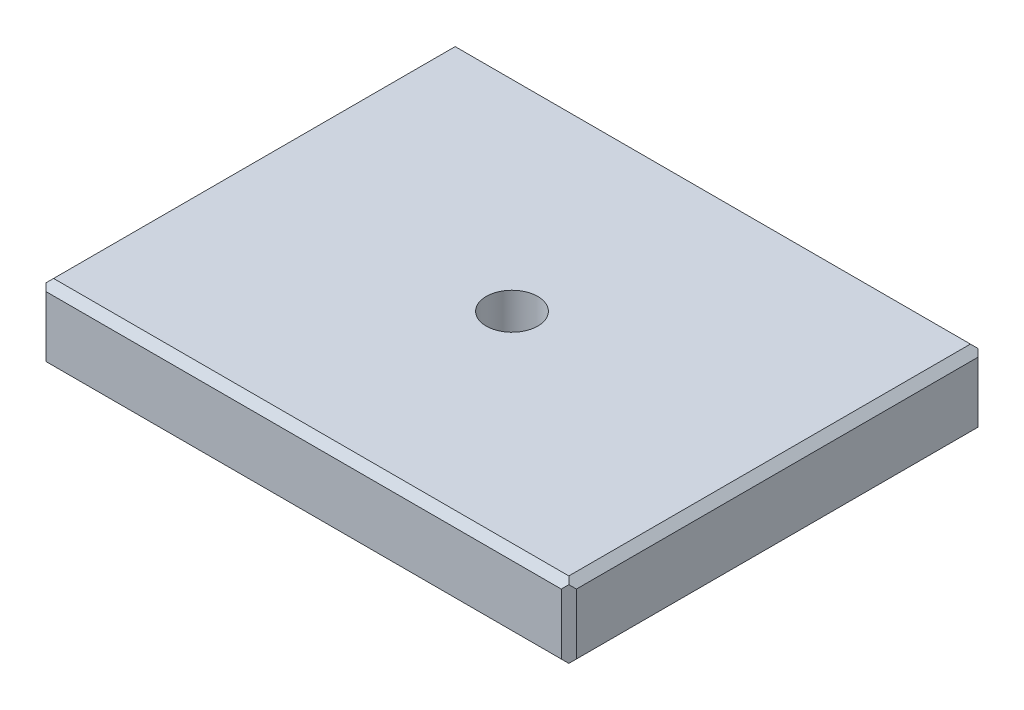
SolidWorks part; units mm, degrees
material "Plain Carbon Steel"
ref_plane "Front Plane" through (0, 0, 0) normal (0, 0, 1) x (1, 0, 0)
ref_plane "Top Plane" through (0, 0, 0) normal (0, 1, 0) x (1, 0, 0)
ref_plane "Right Plane" through (0, 0, 0) normal (1, 0, 0) x (0, 0, -1)
sketch "Sketch1" plane through (0, 0, 0) normal (0, 1, 0) x (1, 0, 0)
  line L1 (-35, -27.5) -> (35, -27.5)
  line L2 (-35, -27.5) -> (-35, 27.5)
  line L3 (-35, 27.5) -> (35, 27.5)
  line L4 (35, -27.5) -> (35, 27.5)
  line L5 (-35, -27.5) -> (35, 27.5) construction
  line L6 (-35, 27.5) -> (35, -27.5) construction
  point P0 (0, 0)
  dimension "D1" = 70
  dimension "D2" = 55
extrude "Boss-Extrude1" add sketch "Sketch1" against normal blind 10
chamfer "Chamfer1" distance 1 angle 45 8 edges at (0, -10, -27.5) (-35, -10, 0) (0, -10, 27.5) (35, -10, 0) (0, 0, 27.5) (-35, 0, 0) (0, 0, -27.5) (35, 0, 0)
hole_wizard "M8 Tapped Hole1" positions "Sketch4" profile "Sketch3" tap size "M8" standard "ISO" end condition through all
sketch "Sketch4" plane through (0, 0, 0) normal (0, 1, 0) x (1, 0, 0)
  point P0 (0, 0)
sketch "Sketch3" plane through (0, 0, 0) normal (1, 0, 0) x (0, 0, 1)
  line L0 (0, 0) -> (0, 10)
  line L1 (0, 10) -> (3.4, 10)
  line L2 (3.4, 10) -> (3.4, 0)
  line L5 (3.4, 0) -> (0, 0)
  line L11 (0, -6.35) -> (0, 107.95) construction
  dimension "Thru Tap Drill Dia." = 6.8
  dimension "Thru Tap Drill Depth" = 10
cosmetic thread "Hole Thread1" parameters "D2"=8
chamfer "Chamfer3" distance 1 angle 45 4 edges at (-35, -5, -27.5) (35, -5, -27.5) (35, -5, 27.5) (-35, -5, 27.5)
